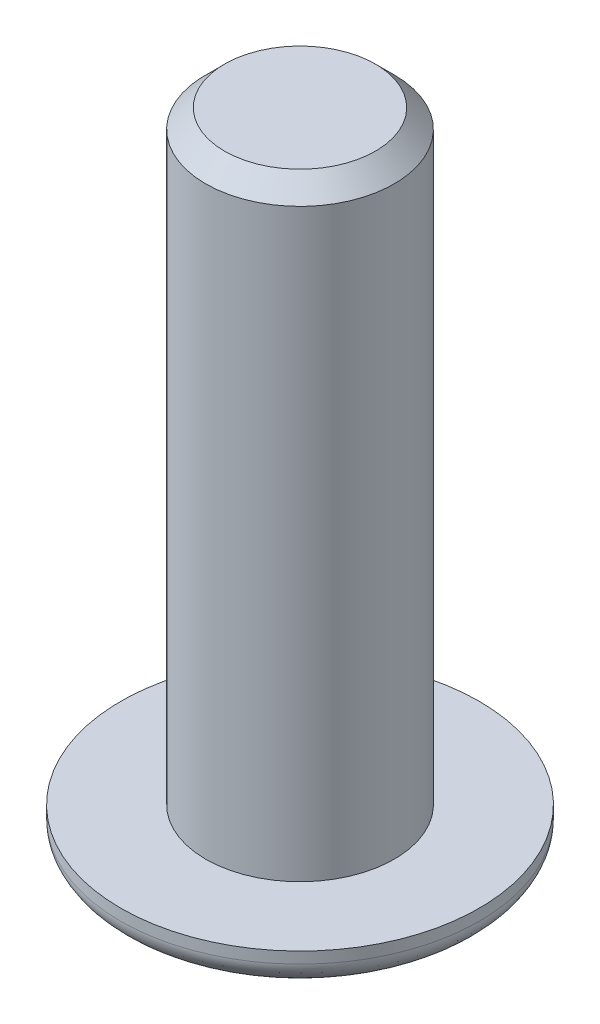
SolidWorks part; units mm, degrees
material "ASTM A36 钢"
ref_plane "前视基准面" through (0, 0, 0) normal (0, 0, 1) x (1, 0, 0)
ref_plane "上视基准面" through (0, 0, 0) normal (0, 1, 0) x (1, 0, 0)
ref_plane "右视基准面" through (0, 0, 0) normal (1, 0, 0) x (0, 0, -1)
sketch "草图1" plane through (0, 0, 0) normal (0, 1, 0) x (1, 0, 0)
  line L1 (0, -1.7321) -> (1.5, -0.866)
  line L2 (1.5, -0.866) -> (1.5, 0.866)
  line L3 (1.5, 0.866) -> (0, 1.7321)
  line L4 (0, 1.7321) -> (-1.5, 0.866)
  line L5 (-1.5, 0.866) -> (-1.5, -0.866)
  line L6 (-1.5, -0.866) -> (0, -1.7321)
  circle A0 centre (0, 0) radius 1.5 construction
  circle A1 centre (0, 0) radius 4.75
extrude "凸台-拉伸1" add sketch "草图1" along normal blind 1.3
sketch "草图2" plane through (0, 1.3, 0) normal (0, 1, 0) x (1, 0, 0)
  circle A0 centre (0, 0) radius 2.5
extrude "凸台-拉伸2" add sketch "草图2" along normal blind 16
chamfer "倒角1" distance 0.5 angle 45 1 edges at (0, 17.3, 2.5)
fillet "圆角1" radius 2 1 edges at (0, 0, 4.75) second distance 1 first distance on face at (0, 0, 4.75)
